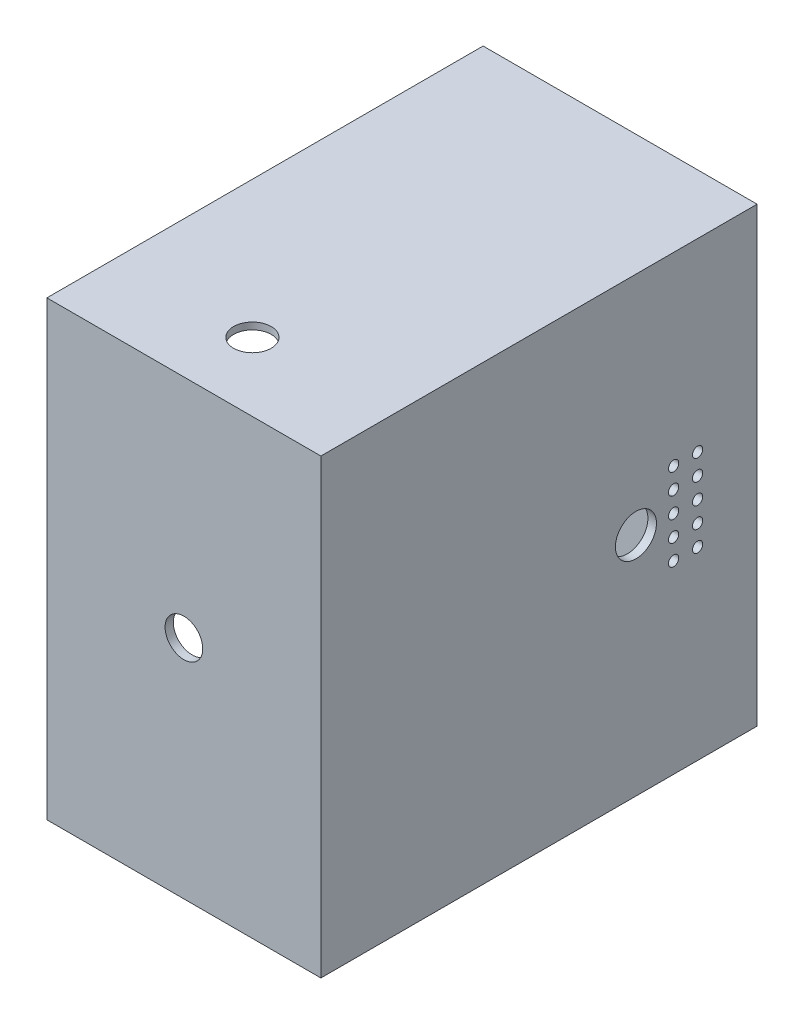
SolidWorks part; units mm, degrees
ref_plane "Front Plane" through (0, 0, 0) normal (0, 0, 1) x (1, 0, 0)
ref_plane "Top Plane" through (0, 0, 0) normal (0, 1, 0) x (1, 0, 0)
ref_plane "Right Plane" through (0, 0, 0) normal (1, 0, 0) x (0, 0, -1)
ref_plane "PZ_p68_625" through (0, 0, 68.625) normal (0, 0, 1) x (1, 0, 0)
sketch "S_box1" plane through (0, 0, 68.625) normal (0, 0, 1) x (1, 0, 0)
  line L0 (-40, -66) -> (40, -66)
  line L1 (40, -66) -> (40, 66)
  line L2 (40, 66) -> (-40, 66)
  line L3 (-40, 66) -> (-40, -66)
  dimension "P1" = 40
  dimension "P2" = 66
  dimension "P3" = 40
  dimension "P4" = 66
  dimension "P5" = 40
  dimension "P6" = 66
  dimension "P7" = 40
  dimension "P8" = 66
extrude "Boss_1" add sketch "S_box1" along normal blind 127.375
ref_plane "PX_p30_500" through (30.5, 0, 0) normal (1, 0, 0) x (0, 0, -1)
sketch "S_cyl2" plane through (30.5, 0, 0) normal (1, 0, 0) x (0, 0, -1)
  circle A0 centre (-115.5, -29) radius 3
  dimension "D1_S_cyl2" = 6
  dimension "P2" = 115.5
  dimension "P3" = 29
extrude "Boss_2" add sketch "S_cyl2" along normal blind 7.5
sketch "S_cyl3" plane through (30.5, 0, 0) normal (1, 0, 0) x (0, 0, -1)
  circle A0 centre (-164.5, -29) radius 3
  dimension "D1_S_cyl3" = 6
  dimension "P2" = 164.5
  dimension "P3" = 29
extrude "Boss_3" add sketch "S_cyl3" along normal blind 7.5
sketch "S_cyl4" plane through (30.5, 0, 0) normal (1, 0, 0) x (0, 0, -1)
  circle A0 centre (-115.5, 29) radius 3
  dimension "D1_S_cyl4" = 6
  dimension "P2" = 115.5
  dimension "P3" = 29
extrude "Boss_4" add sketch "S_cyl4" along normal blind 7.5
sketch "S_cyl5" plane through (30.5, 0, 0) normal (1, 0, 0) x (0, 0, -1)
  circle A0 centre (-164.5, 29) radius 3
  dimension "D1_S_cyl5" = 6
  dimension "P2" = 164.5
  dimension "P3" = 29
extrude "Boss_5" add sketch "S_cyl5" along normal blind 7.5
ref_plane "PZ_p167_500" through (0, 0, 167.5) normal (0, 0, 1) x (1, 0, 0)
sketch "S_box6" plane through (0, 0, 167.5) normal (0, 0, 1) x (1, 0, 0)
  line L0 (-8.2, 43.5) -> (19.4, 43.5)
  line L1 (19.4, 43.5) -> (19.4, 64)
  line L2 (19.4, 64) -> (-8.2, 64)
  line L3 (-8.2, 64) -> (-8.2, 43.5)
  dimension "P1" = 8.2
  dimension "P2" = 43.5
  dimension "P3" = 19.4
  dimension "P4" = 43.5
  dimension "P5" = 19.4
  dimension "P6" = 64
  dimension "P7" = 8.2
  dimension "P8" = 64
extrude "Boss_6" add sketch "S_box6" along normal blind 17
sketch "S_box7" plane through (0, 0, 167.5) normal (0, 0, 1) x (1, 0, 0)
  line L0 (-8.2, -64) -> (19.4, -64)
  line L1 (19.4, -64) -> (19.4, -43.5)
  line L2 (19.4, -43.5) -> (-8.2, -43.5)
  line L3 (-8.2, -43.5) -> (-8.2, -64)
  dimension "P1" = 8.2
  dimension "P2" = 64
  dimension "P3" = 19.4
  dimension "P4" = 64
  dimension "P5" = 19.4
  dimension "P6" = 43.5
  dimension "P7" = 8.2
  dimension "P8" = 43.5
extrude "Boss_7" add sketch "S_box7" along normal blind 17
ref_plane "PZ_p171_500" through (0, 0, 171.5) normal (0, 0, 1) x (1, 0, 0)
sketch "S_box8" plane through (0, 0, 171.5) normal (0, 0, 1) x (1, 0, 0)
  line L0 (-19.4, -8.5) -> (8.2, -8.5)
  line L1 (8.2, -8.5) -> (8.2, 8.5)
  line L2 (8.2, 8.5) -> (-19.4, 8.5)
  line L3 (-19.4, 8.5) -> (-19.4, -8.5)
  dimension "P1" = 19.4
  dimension "P2" = 8.5
  dimension "P3" = 8.2
  dimension "P4" = 8.5
  dimension "P5" = 8.2
  dimension "P6" = 8.5
  dimension "P7" = 19.4
  dimension "P8" = 8.5
extrude "Boss_8" add sketch "S_box8" along normal blind 22.5
ref_plane "PZ_p71_125" through (0, 0, 71.125) normal (0, 0, 1) x (1, 0, 0)
sketch "S_cut9" plane through (0, 0, 71.125) normal (0, 0, 1) x (1, 0, 0)
  line L0 (-41, -63.5) -> (37.5, -63.5)
  line L1 (37.5, -63.5) -> (37.5, 63.5)
  line L2 (37.5, 63.5) -> (-41, 63.5)
  line L3 (-41, 63.5) -> (-41, -63.5)
  dimension "P1" = 41
  dimension "P2" = 63.5
  dimension "P3" = 37.5
  dimension "P4" = 63.5
  dimension "P5" = 37.5
  dimension "P6" = 63.5
  dimension "P7" = 41
  dimension "P8" = 63.5
extrude "Pocket_9" cut sketch "S_cut9" along normal blind 122.375
ref_plane "PZ_p68_525" through (0, 0, 68.525) normal (0, 0, 1) x (1, 0, 0)
sketch "S_hole10" plane through (0, 0, 68.525) normal (0, 0, 1) x (1, 0, 0)
  circle A0 centre (0, -25) radius 1.6
  dimension "D1_S_hole10" = 3.2
  dimension "P2" = 25
extrude "Hole_10" cut sketch "S_hole10" along normal blind 2.7
sketch "S_hole11" plane through (0, 0, 68.525) normal (0, 0, 1) x (1, 0, 0)
  circle A0 centre (0, 25) radius 1.6
  dimension "D1_S_hole11" = 3.2
  dimension "P2" = 25
extrude "Hole_11" cut sketch "S_hole11" along normal blind 2.7
sketch "S_hole12" plane through (0, 0, 68.525) normal (0, 0, 1) x (1, 0, 0)
  circle A0 centre (28, -25) radius 1.6
  dimension "D1_S_hole12" = 3.2
  dimension "P2" = 28
  dimension "P3" = 25
extrude "Hole_12" cut sketch "S_hole12" along normal blind 2.7
sketch "S_hole13" plane through (0, 0, 68.525) normal (0, 0, 1) x (1, 0, 0)
  circle A0 centre (28, 25) radius 1.6
  dimension "D1_S_hole13" = 3.2
  dimension "P2" = 28
  dimension "P3" = 25
extrude "Hole_13" cut sketch "S_hole13" along normal blind 2.7
ref_plane "PX_p37_400" through (37.4, 0, 0) normal (1, 0, 0) x (0, 0, -1)
sketch "S_hole14" plane through (37.4, 0, 0) normal (1, 0, 0) x (0, 0, -1)
  circle A0 centre (-86, -12) radius 1.5
  dimension "D1_S_hole14" = 3
  dimension "P2" = 86
  dimension "P3" = 12
extrude "Hole_14" cut sketch "S_hole14" along normal blind 2.7
sketch "S_hole15" plane through (37.4, 0, 0) normal (1, 0, 0) x (0, 0, -1)
  circle A0 centre (-93, -12) radius 1.5
  dimension "D1_S_hole15" = 3
  dimension "P2" = 93
  dimension "P3" = 12
extrude "Hole_15" cut sketch "S_hole15" along normal blind 2.7
sketch "S_hole16" plane through (37.4, 0, 0) normal (1, 0, 0) x (0, 0, -1)
  circle A0 centre (-86, -6) radius 1.5
  dimension "D1_S_hole16" = 3
  dimension "P2" = 86
  dimension "P3" = 6
extrude "Hole_16" cut sketch "S_hole16" along normal blind 2.7
sketch "S_hole17" plane through (37.4, 0, 0) normal (1, 0, 0) x (0, 0, -1)
  circle A0 centre (-93, -6) radius 1.5
  dimension "D1_S_hole17" = 3
  dimension "P2" = 93
  dimension "P3" = 6
extrude "Hole_17" cut sketch "S_hole17" along normal blind 2.7
sketch "S_hole18" plane through (37.4, 0, 0) normal (1, 0, 0) x (0, 0, -1)
  circle A0 centre (-86, 0) radius 1.5
  dimension "D1_S_hole18" = 3
  dimension "P2" = 86
extrude "Hole_18" cut sketch "S_hole18" along normal blind 2.7
sketch "S_hole19" plane through (37.4, 0, 0) normal (1, 0, 0) x (0, 0, -1)
  circle A0 centre (-93, 0) radius 1.5
  dimension "D1_S_hole19" = 3
  dimension "P2" = 93
extrude "Hole_19" cut sketch "S_hole19" along normal blind 2.7
sketch "S_hole20" plane through (37.4, 0, 0) normal (1, 0, 0) x (0, 0, -1)
  circle A0 centre (-86, 6) radius 1.5
  dimension "D1_S_hole20" = 3
  dimension "P2" = 86
  dimension "P3" = 6
extrude "Hole_20" cut sketch "S_hole20" along normal blind 2.7
sketch "S_hole21" plane through (37.4, 0, 0) normal (1, 0, 0) x (0, 0, -1)
  circle A0 centre (-93, 6) radius 1.5
  dimension "D1_S_hole21" = 3
  dimension "P2" = 93
  dimension "P3" = 6
extrude "Hole_21" cut sketch "S_hole21" along normal blind 2.7
sketch "S_hole22" plane through (37.4, 0, 0) normal (1, 0, 0) x (0, 0, -1)
  circle A0 centre (-86, 12) radius 1.5
  dimension "D1_S_hole22" = 3
  dimension "P2" = 86
  dimension "P3" = 12
extrude "Hole_22" cut sketch "S_hole22" along normal blind 2.7
sketch "S_hole23" plane through (37.4, 0, 0) normal (1, 0, 0) x (0, 0, -1)
  circle A0 centre (-93, 12) radius 1.5
  dimension "D1_S_hole23" = 3
  dimension "P2" = 93
  dimension "P3" = 12
extrude "Hole_23" cut sketch "S_hole23" along normal blind 2.7
sketch "S_hole24" plane through (37.4, 0, 0) normal (1, 0, 0) x (0, 0, -1)
  circle A0 centre (-104, 0) radius 6
  dimension "D1_S_hole24" = 12
  dimension "P2" = 104
extrude "Hole_24" cut sketch "S_hole24" along normal blind 2.7
ref_plane "PX_p30_400" through (30.4, 0, 0) normal (1, 0, 0) x (0, 0, -1)
sketch "S_hole25" plane through (30.4, 0, 0) normal (1, 0, 0) x (0, 0, -1)
  circle A0 centre (-115.5, -29) radius 1.1
  dimension "D1_S_hole25" = 2.2
  dimension "P2" = 115.5
  dimension "P3" = 29
extrude "Hole_25" cut sketch "S_hole25" along normal blind 7.7
sketch "S_hole26" plane through (30.4, 0, 0) normal (1, 0, 0) x (0, 0, -1)
  circle A0 centre (-164.5, -29) radius 1.1
  dimension "D1_S_hole26" = 2.2
  dimension "P2" = 164.5
  dimension "P3" = 29
extrude "Hole_26" cut sketch "S_hole26" along normal blind 7.7
sketch "S_hole27" plane through (30.4, 0, 0) normal (1, 0, 0) x (0, 0, -1)
  circle A0 centre (-115.5, 29) radius 1.1
  dimension "D1_S_hole27" = 2.2
  dimension "P2" = 115.5
  dimension "P3" = 29
extrude "Hole_27" cut sketch "S_hole27" along normal blind 7.7
sketch "S_hole28" plane through (30.4, 0, 0) normal (1, 0, 0) x (0, 0, -1)
  circle A0 centre (-164.5, 29) radius 1.1
  dimension "D1_S_hole28" = 2.2
  dimension "P2" = 164.5
  dimension "P3" = 29
extrude "Hole_28" cut sketch "S_hole28" along normal blind 7.7
ref_plane "PZ_p169_500" through (0, 0, 169.5) normal (0, 0, 1) x (1, 0, 0)
sketch "S_cut29" plane through (0, 0, 169.5) normal (0, 0, 1) x (1, 0, 0)
  line L0 (-6.2, 43.4) -> (17.4, 43.4)
  line L1 (17.4, 43.4) -> (17.4, 64)
  line L2 (17.4, 64) -> (-6.2, 64)
  line L3 (-6.2, 64) -> (-6.2, 43.4)
  dimension "P1" = 6.2
  dimension "P2" = 43.4
  dimension "P3" = 17.4
  dimension "P4" = 43.4
  dimension "P5" = 17.4
  dimension "P6" = 64
  dimension "P7" = 6.2
  dimension "P8" = 64
extrude "Pocket_29" cut sketch "S_cut29" along normal blind 13
ref_plane "PY_p63_400" through (0, 63.4, 0) normal (0, 1, 0) x (1, 0, 0)
sketch "S_hole30" plane through (0, 63.4, 0) normal (0, 1, 0) x (1, 0, 0)
  circle A0 centre (0, -176) radius 5.5
  dimension "D1_S_hole30" = 11
  dimension "P2" = 176
extrude "Hole_30" cut sketch "S_hole30" along normal blind 2.7
sketch "S_cut31" plane through (0, 0, 169.5) normal (0, 0, 1) x (1, 0, 0)
  line L0 (-6.2, -64) -> (17.4, -64)
  line L1 (17.4, -64) -> (17.4, -43.4)
  line L2 (17.4, -43.4) -> (-6.2, -43.4)
  line L3 (-6.2, -43.4) -> (-6.2, -64)
  dimension "P1" = 6.2
  dimension "P2" = 64
  dimension "P3" = 17.4
  dimension "P4" = 64
  dimension "P5" = 17.4
  dimension "P6" = 43.4
  dimension "P7" = 6.2
  dimension "P8" = 43.4
extrude "Pocket_31" cut sketch "S_cut31" along normal blind 13
ref_plane "PY_m66_100" through (0, -66.1, 0) normal (0, 1, 0) x (1, 0, 0)
sketch "S_hole32" plane through (0, -66.1, 0) normal (0, 1, 0) x (1, 0, 0)
  circle A0 centre (0, -176) radius 5.5
  dimension "D1_S_hole32" = 11
  dimension "P2" = 176
extrude "Hole_32" cut sketch "S_hole32" along normal blind 2.7
ref_plane "PZ_p171_400" through (0, 0, 171.4) normal (0, 0, 1) x (1, 0, 0)
sketch "S_cut33" plane through (0, 0, 171.4) normal (0, 0, 1) x (1, 0, 0)
  line L0 (-17.4, -6.5) -> (6.2, -6.5)
  line L1 (6.2, -6.5) -> (6.2, 6.5)
  line L2 (6.2, 6.5) -> (-17.4, 6.5)
  line L3 (-17.4, 6.5) -> (-17.4, -6.5)
  dimension "P1" = 17.4
  dimension "P2" = 6.5
  dimension "P3" = 6.2
  dimension "P4" = 6.5
  dimension "P5" = 6.2
  dimension "P6" = 6.5
  dimension "P7" = 17.4
  dimension "P8" = 6.5
extrude "Pocket_33" cut sketch "S_cut33" along normal blind 22.2
ref_plane "PZ_p193_400" through (0, 0, 193.4) normal (0, 0, 1) x (1, 0, 0)
sketch "S_hole34" plane through (0, 0, 193.4) normal (0, 0, 1) x (1, 0, 0)
  circle A0 centre (0, 0) radius 5.5
  dimension "D1_S_hole34" = 11
extrude "Hole_34" cut sketch "S_hole34" along normal blind 2.7
equation "\"plate_t\" = 3"
equation "\"clearance\" = 0.4"
